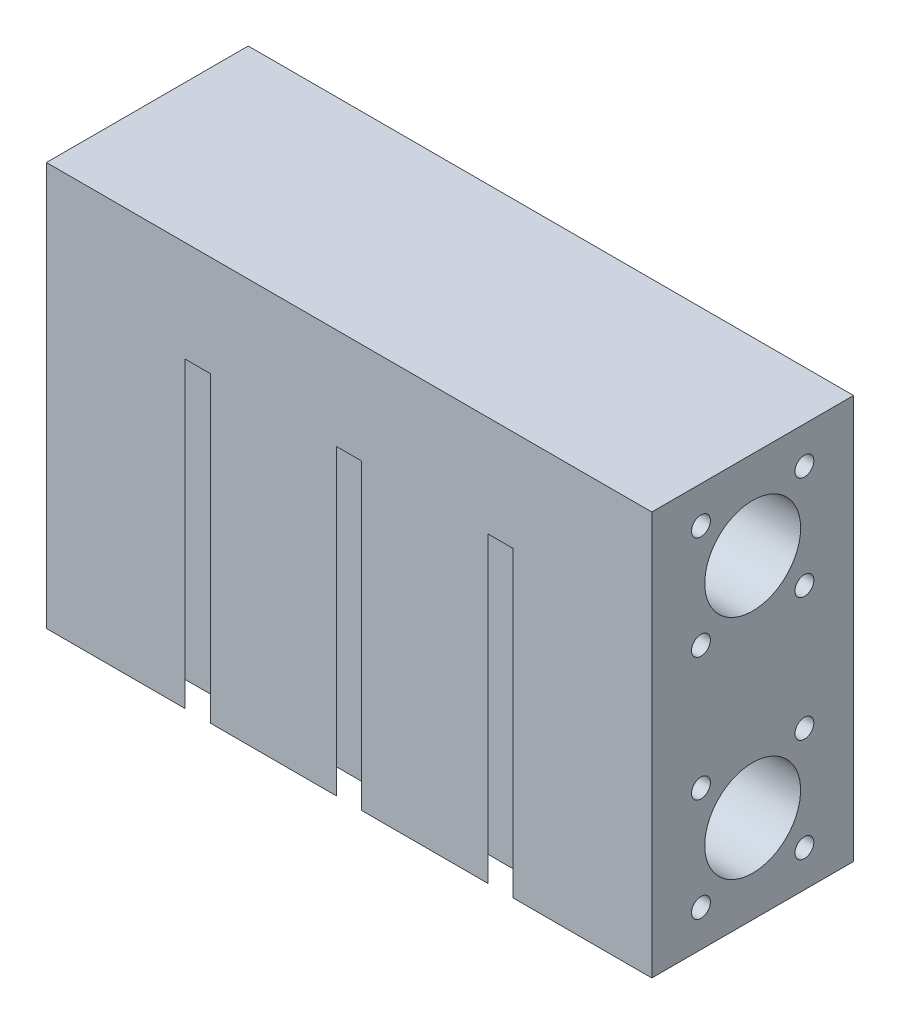
SolidWorks part; units mm, degrees
ref_plane "Front Plane" through (0, 0, 0) normal (0, 0, 1) x (1, 0, 0)
ref_plane "Top Plane" through (0, 0, 0) normal (0, 1, 0) x (1, 0, 0)
ref_plane "Right Plane" through (0, 0, 0) normal (1, 0, 0) x (0, 0, -1)
sketch "Sketch1" plane through (0, 0, 0) normal (0, 0, 1) x (1, 0, 0)
  line L1 (0, 0) -> (120, 0)
  line L2 (0, 0) -> (0, 80)
  line L3 (0, 80) -> (120, 80)
  line L4 (120, 0) -> (120, 80)
  dimension "D1" = 80
  dimension "D2" = 120
extrude "Boss-Extrude1" add sketch "Sketch1" along normal blind 40 contours L3 L4 L1 L2
sketch "Sketch2" plane through (0, 0, 0) normal (-1, 0, 0) x (0, 0, 1)
  line L0 (20, 80) -> (20, 0) construction
  line L1 (40, 80) -> (0, 80) construction
  line L2 (40, 0) -> (0, 0) construction
  line L3 (40, 40) -> (0, 40) construction
  line L4 (40, 0) -> (40, 80) construction
  line L5 (0, 0) -> (0, 80) construction
  line L6 (0, 62.5) -> (40, 62.5) construction
  line L7 (0, 17.5) -> (40, 17.5) construction
  circle A1 centre (30.25, 72.75) radius 1.85
  circle A2 centre (9.75, 72.75) radius 1.85
  circle A3 centre (30.25, 52.25) radius 1.85
  circle A4 centre (9.75, 52.25) radius 1.85
  circle A5 centre (9.75, 27.75) radius 1.85
  circle A6 centre (30.25, 27.75) radius 1.85
  circle A7 centre (30.25, 7.25) radius 1.85
  circle A9 centre (9.75, 7.25) radius 1.85
  dimension "D4" = 3.7
  dimension "D1" = 22.5
  dimension "D2" = 9.75
  dimension "D3" = 7.25
extrude "linear-bearing-screw-cuts" cut sketch "Sketch2" against normal blind 14
sketch "Sketch3" plane through (0, 0, 0) normal (-1, 0, 0) x (0, 0, 1)
  line L0 (20, 80) -> (20, 0) construction
  line L1 (40, 80) -> (0, 80) construction
  line L2 (40, 0) -> (0, 0) construction
  line L3 (0, 40) -> (40, 40) construction
  line L4 (0, 0) -> (0, 80) construction
  line L5 (40, 0) -> (40, 80) construction
  line L6 (0, 62.5) -> (40, 62.5) construction
  line L7 (0, 17.5) -> (40, 17.5) construction
  circle A0 centre (20, 62.5) radius 9.5
  circle A2 centre (20, 17.5) radius 9.5
  dimension "D2" = 19
  dimension "D1" = 45
extrude "linear-bearings-hole" cut sketch "Sketch3" against normal blind 55
sketch "Sketch4" plane through (120, 0, 0) normal (1, 0, 0) x (0, 0, -1)
  line L0 (-20, 80) -> (-20, 0) construction
  line L1 (-40, 80) -> (0, 80) construction
  line L2 (-40, 0) -> (0, 0) construction
  line L3 (-40, 40) -> (0, 40) construction
  line L4 (-40, 0) -> (-40, 80) construction
  line L5 (0, 0) -> (0, 80) construction
  line L6 (-40, 62.5) -> (0, 62.5) construction
  line L7 (-40, 17.5) -> (0, 17.5) construction
  circle A0 centre (-9.75, 72.75) radius 1.875
  circle A1 centre (-30.25, 72.75) radius 1.875
  circle A2 centre (-9.75, 52.25) radius 1.875
  circle A3 centre (-30.25, 52.25) radius 1.875
  circle A4 centre (-30.25, 27.75) radius 1.875
  circle A5 centre (-9.75, 27.75) radius 1.875
  circle A6 centre (-9.75, 7.25) radius 1.875
  circle A7 centre (-30.25, 7.25) radius 1.875
  point P18 (0, 0)
  dimension "D2" = 3.75
  dimension "D1" = 45
  dimension "D3" = 7.25
  dimension "D4" = 9.75
extrude "linear-bearing-screw-cuts2" cut sketch "Sketch4" against normal blind 14
sketch "Sketch5" plane through (120, 0, 0) normal (1, 0, 0) x (0, 0, -1)
  line L0 (-20, 80) -> (-20, 0) construction
  line L1 (-40, 80) -> (0, 80) construction
  line L2 (-40, 0) -> (0, 0) construction
  line L3 (0, 40) -> (-40, 40) construction
  line L4 (0, 0) -> (0, 80) construction
  line L5 (-40, 0) -> (-40, 80) construction
  line L6 (-40, 62.5) -> (0, 62.5) construction
  line L7 (-40, 17.5) -> (0, 17.5) construction
  circle A0 centre (-20, 62.5) radius 9.5
  circle A1 centre (-20, 17.5) radius 9.5
  dimension "D2" = 19
  dimension "D1" = 45
extrude "Cut-Extrude4" cut sketch "Sketch5" against normal blind 55
sketch "Sketch10" plane through (0, 0, 0) normal (0, -1, 0) x (1, 0, 0)
  line L0 (87.5, 40) -> (82.5, 35)
  line L1 (0, 40) -> (120, 40) construction
  line L2 (82.5, 35) -> (97.5, 35)
  line L3 (97.5, 35) -> (92.5, 40)
  line L4 (92.5, 40) -> (87.5, 40)
  line L5 (60, 40) -> (60, 0) construction
  line L6 (0, 0) -> (120, 0) construction
  line L7 (75, 40) -> (75, 0) construction
  line L8 (120, 40) -> (120, 0) construction
  line L9 (52.5, 35) -> (57.5, 40)
  line L10 (67.5, 35) -> (52.5, 35)
  line L11 (62.5, 40) -> (67.5, 35)
  line L12 (57.5, 40) -> (62.5, 40)
  line L13 (22.5, 35) -> (27.5, 40)
  line L14 (37.5, 35) -> (22.5, 35)
  line L15 (32.5, 40) -> (37.5, 35)
  line L16 (27.5, 40) -> (32.5, 40)
  point P12 (90, 40)
  point P15 (92.8471, 40)
  point P16 (88.7649, 40)
  point P17 (92.5803, 38.4427)
  dimension "D1" = 30
  dimension "D2" = 15
  dimension "D3" = 45
  dimension "D4" = 5
  dimension "D5" = 45
  dimension "D6" = 45
extrude "Cut-Extrude8" cut sketch "Sketch10" against normal blind 60
